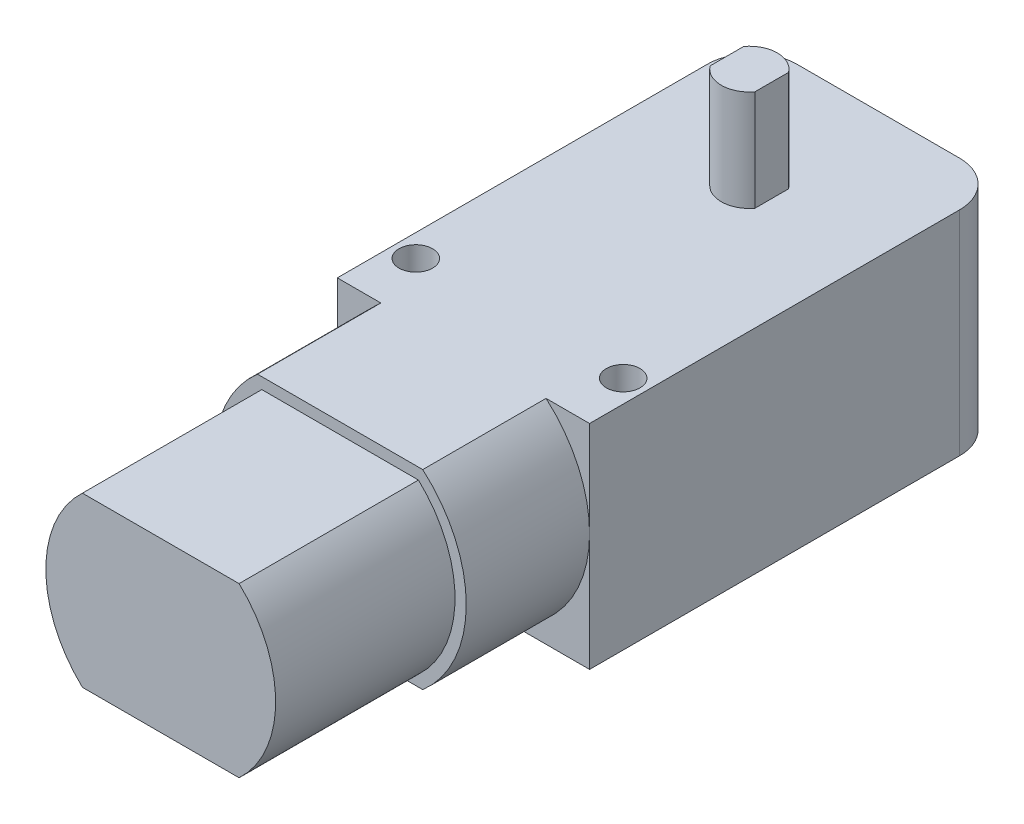
SolidWorks part; units mm, degrees
ref_plane "Front Plane" through (0, 0, 0) normal (0, 0, 1) x (1, 0, 0)
ref_plane "Top Plane" through (0, 0, 0) normal (0, 1, 0) x (1, 0, 0)
ref_plane "Right Plane" through (0, 0, 0) normal (1, 0, 0) x (0, 0, -1)
sketch "Sketch1" plane through (0, 0, 0) normal (0, 0, 1) x (1, 0, 0)
  line L1 (11.25, 9.5) -> (-11.25, 9.5)
  line L2 (11.25, 9.5) -> (11.25, -9.5)
  line L3 (11.25, -9.5) -> (-11.25, -9.5)
  line L4 (-11.25, 9.5) -> (-11.25, -9.5)
  line L5 (11.25, 9.5) -> (-11.25, -9.5) construction
  line L6 (11.25, -9.5) -> (-11.25, 9.5) construction
  point P0 (0, 0)
  dimension "D1" = 22.5
  dimension "D2" = 19
extrude "Boss-Extrude1" add sketch "Sketch1" along normal blind 37
ref_plane "Plane1" through (0, 0, 37) normal (0, 0, 1) x (1, 0, 0)
sketch "Sketch3" plane through (0, 0, 37) normal (0, 0, 1) x (1, 0, 0)
  line L0 (-7.3697, -7.5) -> (7.3697, -7.5)
  line L1 (11.25, 9.5) -> (-11.25, 9.5) construction
  line L3 (-7.3697, 9.5) -> (7.3697, 9.5)
  line L7 (3.6389, 8.9364) -> (3.2149, 8.9364)
  arc A2 (-7.3697, 9.5) -> (-7.3697, -7.5) centre (0, 1) ccw
  arc A3 (7.3697, -7.5) -> (7.3697, 9.5) centre (0, 1) ccw
  dimension "D2" = 22.5
extrude "Boss-Extrude2" add sketch "Sketch3" along normal blind 11 contours A3 A2 L0 region at (0, 1, 37)
sketch "Sketch4" plane through (0, 0, 48) normal (0, 0, 1) x (1, 0, 0)
  line L0 (-2.0762, 8.5) -> (5.2317, 8.5)
  line L1 (-5.9412, -6.5) -> (4.6471, -6.5)
  line L6 (6.9866, 8.5) -> (-6.9866, 8.5)
  line L7 (-6.9866, -6.5) -> (6.9866, -6.5)
  arc A0 (-6.9866, 8.5) -> (-6.9866, -6.5) centre (0, 1) ccw
  arc A1 (6.9866, -6.5) -> (6.9866, 8.5) centre (0, 1) ccw
extrude "Boss-Extrude3" add sketch "Sketch4" along normal blind 16 contours L7 A1 L6 L0 A0 L1 region at (0, 1, 48)
fillet "Fillet1" radius 4 2 edges at (11.25, 0, 0) (-11.25, 0, 0)
sketch "Sketch5" plane through (0, 9.5, 0) normal (0, 1, 0) x (1, 0, 0)
  line L0 (11.25, -37) -> (7.3697, -37) construction
  line L1 (-2, -10) -> (-2, -13)
  line L2 (-5.775, -37) -> (5.775, -37) construction
  line L3 (-11.25, -37) -> (-11.25, -4) construction
  line L4 (7.25, 0) -> (-7.25, 0) construction
  line L5 (2, -10) -> (2, -13)
  line L6 (11.25, -37) -> (11.25, -4) construction
  circle A0 centre (-9.25, -32) radius 1.5
  circle A1 centre (9.25, -32) radius 1.5
  arc A2 (2, -10) -> (-2, -10) centre (0, -11.5) ccw
  arc A3 (-2, -13) -> (2, -13) centre (0, -11.5) ccw
  point P3 (0, -11.5)
  point P18 (-2, -11.5)
  point P21 (2, -11.5)
  dimension "D1" = 3
  dimension "D2" = 5
  dimension "D3" = 2
  dimension "D4" = 5
  dimension "D5" = 11.5
  dimension "D6" = 3
  dimension "D7" = 5
  dimension "D8" = 2
sketch "Sketch6" plane through (0, 0, 0) normal (0, 0, -1) x (-1, 0, 0)
  line L0 (-7.25, 9.5) -> (7.25, 9.5) construction
  line L4 (-2.4808, -0.5) -> (2.5192, -0.5)
  line L5 (-2.4808, -0.5) -> (-2.4808, 2)
  line L6 (-2.4808, 2) -> (2.5192, 2)
  line L7 (2.5192, -0.5) -> (2.5192, 2)
  dimension "D1" = 5
  dimension "D2" = 2.5
  dimension "D3" = 7.5
extrude "Boss-Extrude4" add sketch "Sketch6" along normal blind 5
sketch "Sketch7" plane through (0, 2, 0) normal (0, 1, 0) x (1, 0, 0)
  line L0 (-0.0192, 5) -> (0, 0)
  line L1 (-2.5192, 5) -> (2.4808, 5) construction
  circle A0 centre (-0.0096, 2.5) radius 1.5
extrude "Cut-Extrude1" cut sketch "Sketch7" against normal blind 5 contours A0
extrude "Cut-Extrude3" cut sketch "Sketch5" against normal blind 19 contours A0 | A1 region at (-9.25, 9.5, 32) region at (9.25, 9.5, 32)
extrude "Boss-Extrude5" add sketch "Sketch5<5>" along normal blind 9 contours A2 L1 A3 L5
sketch "Sketch5<5>" plane through (0, 9.5, 0) normal (0, 1, 0) x (1, 0, 0) same geometry as "Sketch5"
sketch "Sketch8" plane through (0, -9.5, 0) normal (0, -1, 0) x (1, 0, 0)
  line L0 (11.25, 37) -> (11.25, 4) construction
  line L1 (7.25, 0) -> (-7.25, 0) construction
  line L2 (-11.25, 4) -> (-11.25, 37) construction
  line L3 (-11.25, 37) -> (-7.3697, 37) construction
  line L4 (-7.25, 0) -> (7.25, 0)
  line L5 (11.25, 4) -> (11.25, 37)
  line L6 (11.25, 37) -> (-11.25, 37)
  line L7 (-11.25, 37) -> (-11.25, 4)
  line L8 (-7.25, 0) -> (7.25, 0)
  line L9 (11.25, 4) -> (11.25, 37)
  line L10 (11.25, 37) -> (-11.25, 37)
  line L11 (-11.25, 37) -> (-11.25, 4)
  line L12 (-7.3697, 37) -> (-7.3697, 48) construction
  line L13 (-7.3697, 48) -> (7.3697, 48) construction
  line L14 (7.3697, 48) -> (7.3697, 37) construction
  line L15 (7.3697, 37) -> (11.25, 37) construction
  line L16 (11.25, 4) -> (11.25, 37)
  line L17 (-7.25, 0) -> (7.25, 0)
  line L18 (-11.25, 37) -> (-11.25, 4)
  line L19 (-7.3697, 37) -> (-11.25, 37)
  line L20 (-7.3697, 48) -> (-7.3697, 37)
  line L21 (7.3697, 48) -> (-7.3697, 48)
  line L22 (7.3697, 37) -> (7.3697, 48)
  line L23 (11.25, 37) -> (7.3697, 37)
  line L24 (11.25, 4) -> (11.25, 37)
  line L25 (-7.25, 0) -> (7.25, 0)
  line L26 (-11.25, 37) -> (-11.25, 4)
  line L27 (-7.3697, 37) -> (-11.25, 37)
  line L28 (-7.3697, 48) -> (-7.3697, 37)
  line L29 (7.3697, 48) -> (-7.3697, 48)
  line L30 (7.3697, 37) -> (7.3697, 48)
  line L31 (11.25, 37) -> (7.3697, 37)
  line L32 (-7.25, 0) -> (7.25, 0) construction
  line L33 (11.25, 4) -> (11.25, 37) construction
  line L34 (11.25, 37) -> (-11.25, 37) construction
  line L35 (-11.25, 37) -> (-11.25, 4) construction
  line L36 (11.25, 37) -> (11.25, 4)
  line L37 (7.25, 0) -> (-7.25, 0)
  line L38 (-11.25, 4) -> (-11.25, 37)
  line L39 (-11.25, 37) -> (-7.3697, 37)
  line L40 (-7.3697, 37) -> (-7.3697, 48)
  line L41 (-7.3697, 48) -> (7.3697, 48)
  line L42 (7.3697, 48) -> (7.3697, 37)
  line L43 (7.3697, 37) -> (11.25, 37)
  line L44 (-7.25, 0) -> (7.25, 0)
  line L45 (11.25, 4) -> (11.25, 37)
  line L46 (11.25, 37) -> (-11.25, 37)
  line L47 (-11.25, 37) -> (-11.25, 4)
  line L48 (0, 37) -> (0, 0)
  line L50 (-2, 13) -> (-2, 10)
  line L51 (2, 13) -> (2, 10)
  arc A0 (7.25, 0) -> (11.25, 4) centre (7.25, 4) ccw construction
  arc A1 (-11.25, 4) -> (-7.25, 0) centre (-7.25, 4) ccw construction
  arc A2 (7.25, 0) -> (11.25, 4) centre (7.25, 4) ccw
  arc A3 (-11.25, 4) -> (-7.25, 0) centre (-7.25, 4) ccw
  arc A4 (7.25, 0) -> (11.25, 4) centre (7.25, 4) ccw
  arc A5 (-11.25, 4) -> (-7.25, 0) centre (-7.25, 4) ccw
  arc A6 (7.25, 0) -> (11.25, 4) centre (7.25, 4) ccw
  arc A7 (-11.25, 4) -> (-7.25, 0) centre (-7.25, 4) ccw
  arc A8 (7.25, 0) -> (11.25, 4) centre (7.25, 4) ccw
  arc A9 (-11.25, 4) -> (-7.25, 0) centre (-7.25, 4) ccw
  arc A10 (7.25, 0) -> (11.25, 4) centre (7.25, 4) ccw construction
  arc A11 (-11.25, 4) -> (-7.25, 0) centre (-7.25, 4) ccw construction
  arc A12 (7.25, 0) -> (11.25, 4) centre (7.25, 4) ccw
  arc A13 (-11.25, 4) -> (-7.25, 0) centre (-7.25, 4) ccw
  arc A14 (7.25, 0) -> (11.25, 4) centre (7.25, 4) ccw
  arc A15 (-11.25, 4) -> (-7.25, 0) centre (-7.25, 4) ccw
  arc A16 (-2, 10) -> (2, 10) centre (0, 11.5) ccw
  arc A17 (2, 13) -> (-2, 13) centre (0, 11.5) ccw
  point P26 (0, 11.5)
  point P30 (-2, 11.5)
  point P33 (2, 11.5)
  dimension "D3" = 11.5
  dimension "D1" = 0
  dimension "D2" = 0
extrude "Boss-Extrude6" add sketch "Sketch8" along normal blind 9 contours A16 L51 A17 L50
